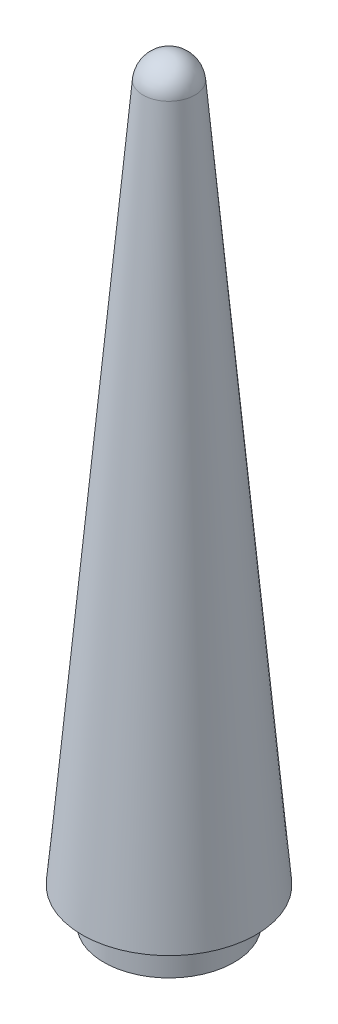
SolidWorks part; units mm, degrees
material "6061 Alloy"
ref_plane "Front Plane" through (0, 0, 0) normal (0, 0, 1) x (1, 0, 0)
ref_plane "Top Plane" through (0, 0, 0) normal (0, 1, 0) x (1, 0, 0)
ref_plane "Right Plane" through (0, 0, 0) normal (1, 0, 0) x (0, 0, -1)
sketch "Sketch2" plane through (0, 0, 0) normal (0, 0, 1) x (1, 0, 0)
  line L0 (0, -3.7271) -> (0, 141.5732)
  line L1 (0, 141.5732) -> (12.7121, -3.7271)
  line L2 (12.7121, -3.7271) -> (9.525, -3.7271)
  line L3 (9.525, -3.7271) -> (9.525, -8.8071)
  line L4 (9.525, -8.8071) -> (0, -8.8071)
  line L5 (0, -8.8071) -> (0, -3.7271)
  line L6 (0, 101.6683) -> (-2.1023, 101.6683) construction
  line L7 (0, -200166.8953) -> (0, 200141.5732) construction
  line L8 (12.7121, -3.7271) -> (-12.7121, -3.7271) construction
  line L9 (0, 141.5732) -> (26.9875, -166.8953) construction
  arc A0 (3.7955, 98.1904) -> (0, 101.6683) centre (0, 97.8583) ccw
revolve "Revolve1" add sketch "Sketch2" angle 360 about L0 region at (4.5077, 36.3669, 0)
sketch "Sketch3" plane through (0, -8.8071, 0) normal (0, -1, 0) x (1, 0, 0)
  point P0 (0, 0)
hole_wizard "1/4-20 Tapped Hole1" positions "Sketch3" profile "Sketch4" tap size "1/4-20" standard "ANSI Inch"
sketch "Sketch4" plane through (0, -8.8071, 0) normal (1, 0, 0) x (0, 0, -1)
  line L0 (0, 0) -> (0, 65.0338)
  line L1 (0, 65.0338) -> (2.5527, 63.5)
  line L2 (2.5527, 63.5) -> (2.5527, 1.2573)
  line L3 (2.5527, 1.2573) -> (3.81, 0)
  line L5 (3.81, 0) -> (0, 0)
  line L6 (-2.5527, 1.2573) -> (-3.81, 0) construction
  line L10 (0, 65.0338) -> (-2.5527, 63.5) construction
  line L11 (0, -6.35) -> (0, 107.95) construction
  dimension "Tap Drill Dia." = 5.1054
  dimension "Tap Drill Depth" = 63.5
  dimension "Near C'Sink Dia." = 7.62
  dimension "Near C'Sink Angle" = 90
  dimension "Drill Angle" = 118
cosmetic thread "Hole Thread1" parameters "D1"=50.8, "D2"=6.35
